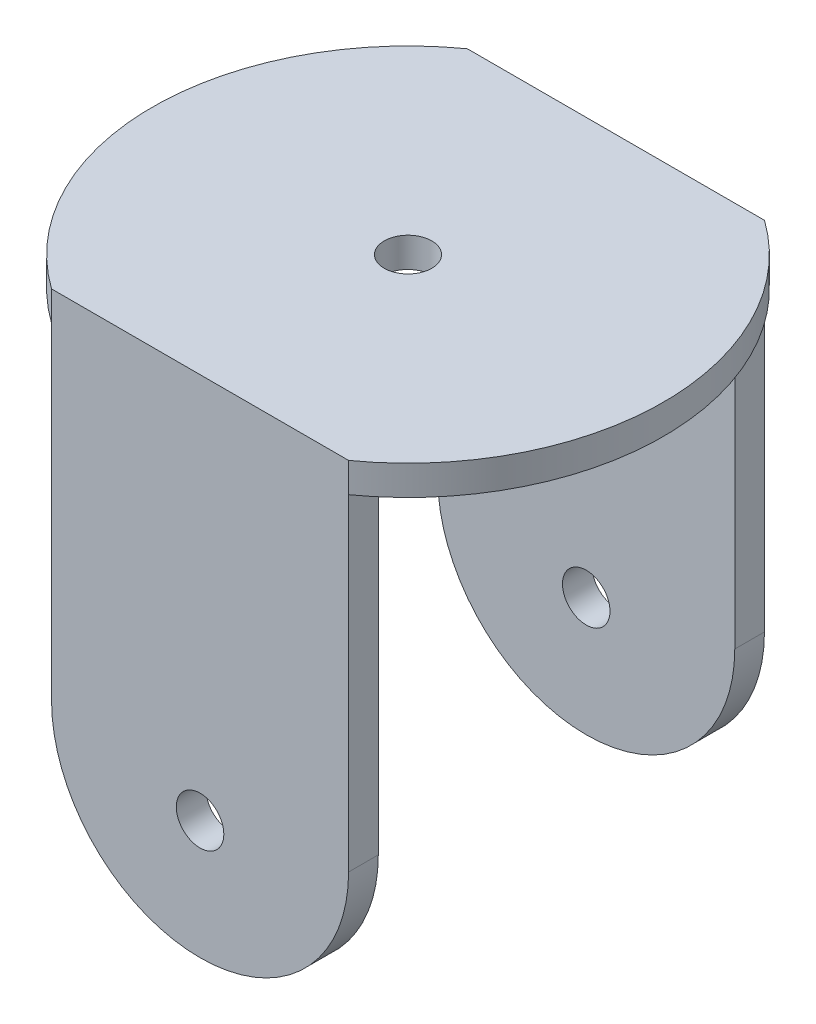
SolidWorks part; units mm, degrees
ref_plane "前视基准面" through (0, 0, 0) normal (0, 0, 1) x (1, 0, 0)
ref_plane "上视基准面" through (0, 0, 0) normal (0, 1, 0) x (1, 0, 0)
ref_plane "右视基准面" through (0, 0, 0) normal (1, 0, 0) x (0, 0, -1)
other "Configuration Table"
sketch "草图1" plane through (0, 0, 0) normal (0, 0, 1) x (1, 0, 0)
  line L1 (-25, 40) -> (25, 40)
  line L2 (-25, 40) -> (-25, -40)
  line L3 (-25, -40) -> (25, -40)
  line L4 (25, 40) -> (25, -40)
  line L5 (-25, 40) -> (25, -40) construction
  line L6 (-25, -40) -> (25, 40) construction
  point P0 (0, 0)
  dimension "D1" = 50
  dimension "D2" = 80
extrude "凸台-拉伸1" add sketch "草图1" along normal blind 5
ref_plane "基准面1" through (0, 0, 65) normal (0, 0, 1) x (1, 0, 0)
sketch "草图2" plane through (0, 0, 65) normal (0, 0, 1) x (1, 0, 0)
  line L4 (25, -40) -> (25, 40)
  line L5 (25, 40) -> (-25, 40)
  line L6 (-25, 40) -> (-25, -40)
  line L7 (-25, -40) -> (25, -40)
  line L8 (25, -40) -> (25, 40)
  line L9 (25, 40) -> (-25, 40)
  line L10 (-25, 40) -> (-25, -40)
  line L11 (-25, -40) -> (25, -40)
  dimension "D1" = 0
extrude "凸台-拉伸2" add sketch "草图2" along normal blind 5 separate body
sketch "草图3" plane through (0, 40, 0) normal (0, 1, 0) x (1, 0, 0)
  line L0 (0, 13.9101) -> (0, -88.6419) construction
  line L1 (-25, 0) -> (25, 0)
  line L2 (-25, 0) -> (-25, -70) construction
  line L3 (-25, -70) -> (25, -70)
  line L4 (25, 0) -> (25, -70) construction
  line L5 (-25, -35) -> (52.7775, -35) construction
  arc A0 (-25, 0) -> (-25, -70) centre (0, -35) ccw
  arc A1 (25, -70) -> (25, 0) centre (0, -35) ccw
extrude "凸台-拉伸3" add sketch "草图3" along normal blind 5
sketch "草图4" plane through (0, 0, 70) normal (0, 0, 1) x (1, 0, 0)
  line L0 (0, 56.3532) -> (0, -60.1266) construction
  line L1 (-25, -40) -> (25, -40) construction
  circle A0 centre (0, -20) radius 4
  dimension "D1" = 8
  dimension "D2" = 20
extrude "切除-拉伸1" cut sketch "草图4" against normal through all
sketch "草图5" plane through (0, 45, 0) normal (0, 1, 0) x (1, 0, 0)
  line L0 (-25, -35) -> (44.9291, -35) construction
  line L2 (0, 9.9063) -> (0, -82.4542) construction
  line L3 (-25, -70) -> (25, -70) construction
  circle A0 centre (0, -35) radius 4
  dimension "D1" = 8
  dimension "D2" = 35
extrude "切除-拉伸2" cut sketch "草图5" against normal through all
fillet "圆角1" radius 25 4 edges at (-25, -40, 2.5) (25, -40, 2.5) (25, -40, 67.5) (-25, -40, 67.5)
